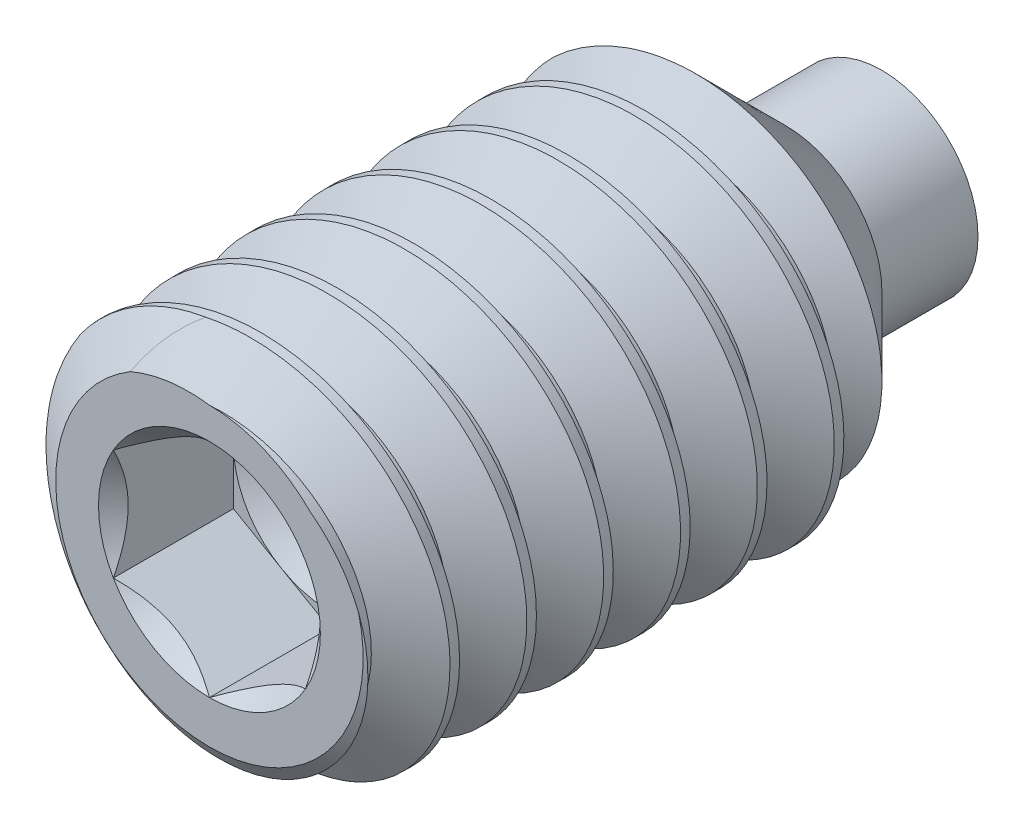
SolidWorks part; units mm, degrees
ref_plane "Front" through (0, 0, 0) normal (0, 0, 1) x (1, 0, 0)
ref_plane "Top" through (0, 0, 0) normal (0, 1, 0) x (1, 0, 0)
ref_plane "Right" through (0, 0, 0) normal (1, 0, 0) x (0, 0, -1)
sketch "Sketch22" plane through (0, 0, 0) normal (1, 0, 0) x (0, 0, -1)
  line L0 (-5.5563, 0) -> (-5.5563, 2.54)
  line L1 (-5.5563, 2.54) -> (-5.1116, 3.175)
  line L2 (-5.1116, 3.175) -> (2.3813, 3.175)
  line L3 (2.3813, 3.175) -> (3.9688, 1.5875)
  line L4 (-5.5563, 2.54) -> (-5.5563, -2.54) construction
  line L5 (5.5563, 0) -> (-5.5563, 0)
  line L6 (0, 3.175) -> (0, -3.175) construction
  line L8 (3.9688, 1.5875) -> (5.5563, 1.5875)
  line L9 (-3.7464, -3.175) -> (3.7464, -3.175) construction
  line L10 (5.5563, 1.5875) -> (5.5563, 0)
  line L11 (5.5563, 1.5875) -> (5.5563, -1.5875) construction
  dimension "D1" = 45
  dimension "Dia" = 6.35
  dimension "D2" = 5.08
  dimension "Length" = 9.525
  dimension "D3" = 35
  dimension "A" = 3.175
  dimension "B" = 1.5875
revolve "Revolve1" add sketch "Sketch22" angle 360 about L5
ref_plane "Plane1" through (0, 0, -3.9688) normal (0, 0, 1) x (1, 0, 0)
sketch "Sketch27" plane through (0, 0, -3.9688) normal (0, 0, 1) x (1, 0, 0)
  circle A0 centre (0, 0) radius 3.175 construction
  circle A1 centre (0, 0) radius 3.175
curve "Helix/Spiral1" pitch 1.27 height 12.065 radius 3.175 centre (0, 0, -3.9688) axis (0, 0, 1) start towards (0, 1, 0)
sketch "Sketch28" plane through (0, 0, 0) normal (1, 0, 0) x (0, 0, -1)
  line L0 (3.9688, 3.175) -> (5.08, 3.175)
  line L1 (5.08, 3.175) -> (4.6037, 2.3501)
  line L2 (4.6037, 2.3501) -> (4.445, 2.3501)
  line L3 (4.445, 2.3501) -> (3.9688, 3.175)
  line L4 (4.2069, 2.7626) -> (4.8419, 2.7626) construction
  line L6 (-5.1116, 3.175) -> (2.3813, 3.175) construction
  line L7 (3.9688, 3.4925) -> (3.9688, -3.4925) construction
  dimension "D1" = 0.1588
  dimension "D2" = 0.635
  dimension "D3" = 60
sweep "Cut-Sweep2" cut profiles "Sketch28" path "Helix/Spiral1"
sketch "Sketch23" plane through (0, 0, 5.5563) normal (0, 0, 1) x (1, 0, 0)
  line L1 (0, 1.8331) -> (-1.5875, 0.9165)
  line L2 (-1.5875, 0.9165) -> (-1.5875, -0.9165)
  line L3 (-1.5875, -0.9165) -> (0, -1.8331)
  line L4 (0, -1.8331) -> (1.5875, -0.9165)
  line L5 (1.5875, -0.9165) -> (1.5875, 0.9165)
  line L6 (1.5875, 0.9165) -> (0, 1.8331)
  circle A0 centre (0, 0) radius 1.5875 construction
  dimension "Hex" = 3.175
extrude "Cut-Extrude10" cut sketch "Sketch23" against normal blind 1.9844
sketch "Sketch24" plane through (0, 0, 5.5563) normal (0, 0, 1) x (1, 0, 0)
  circle A0 centre (0, 0) radius 1.8331
extrude "Cut-Extrude11" cut sketch "Sketch24" against normal through all draft 45
sketch "Sketch26" plane through (0, 0, 3.5719) normal (0, 0, 1) x (1, 0, 0)
  circle A0 centre (0, 0) radius 1.5875 construction
  circle A1 centre (0, 0) radius 1.5875
extrude "Cut-Extrude12" cut sketch "Sketch26" against normal through all draft 60
sketch "Sketch30" plane through (0, 0, 0) normal (1, 0, 0) x (0, 0, -1)
  line L0 (-5.1116, 3.175) -> (2.3813, 3.175) construction
  line L1 (-5.5563, 0) -> (-5.5563, 2.54) construction
  line L2 (3.9688, 3.175) -> (3.9688, -3.175) construction
  line L3 (-3.7464, -3.175) -> (3.7464, -3.175) construction
  point P0 (-5.5563, 3.175)
  point P1 (5.5563, 3.175)
  point P2 (5.5563, -3.175)
  point P11 (-0.4763, -3.175)
  dimension "D1" = 4.445
equation "\"D1@Sketch28\" = \"D4@Helix/Spiral1\" * .125"
equation "\"D3@Helix/Spiral1\" = \"Length@Sketch22\" +  ( \"D4@Helix/Spiral1\" * 2 ) "
equation "\"D1@Sketch30\" = \"D4@Helix/Spiral1\" * 3.5"
equation "\"hex Depth@Cut-Extrude10\" = \"Hex@Sketch23\" * .625"
equation "\"D2@Sketch28\" = \"D4@Helix/Spiral1\" * .5"
equation "\"D2@Sketch22\" = \"Dia@Sketch22\" * .8"
